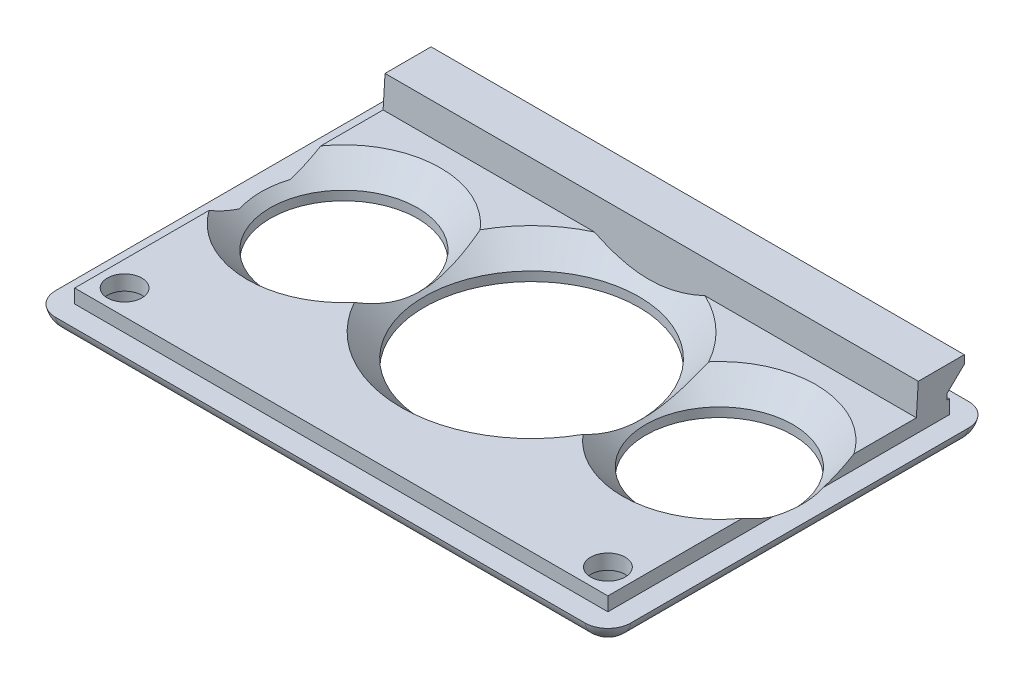
SolidWorks part; units mm, degrees
ref_plane "Front Plane" through (0, 0, 0) normal (0, 0, 1) x (1, 0, 0)
ref_plane "Top Plane" through (0, 0, 0) normal (0, 1, 0) x (1, 0, 0)
ref_plane "Right Plane" through (0, 0, 0) normal (1, 0, 0) x (0, 0, -1)
sketch "Sketch1" plane through (0, 0, 0) normal (0, 1, 0) x (1, 0, 0)
  line L1 (-1.2463, 1.173) -> (73.7537, 1.173)
  line L2 (-1.2463, 1.173) -> (-1.2463, 51.173)
  line L3 (-1.2463, 51.173) -> (73.7537, 51.173)
  line L4 (73.7537, 1.173) -> (73.7537, 51.173)
  dimension "D1" = 50
  dimension "D2" = 75
extrude "Boss-Extrude1" add sketch "Sketch1" along normal blind 2.4
sketch "Sketch2" plane through (0, 2.4, 0) normal (0, 1, 0) x (1, 0, 0)
  line L0 (36.2537, 51.173) -> (36.2537, 1.173) construction
  line L1 (73.7537, 51.173) -> (-1.2463, 51.173) construction
  line L2 (-1.2463, 1.173) -> (73.7537, 1.173) construction
  line L3 (-1.2463, 51.173) -> (-1.2463, 1.173) construction
  line L4 (1.5037, 48.423) -> (71.0037, 48.423)
  line L5 (1.5037, 48.423) -> (1.5037, 3.923)
  line L6 (1.5037, 3.923) -> (71.0037, 3.923)
  line L7 (71.0037, 48.423) -> (71.0037, 3.923)
  line L8 (1.5037, 48.423) -> (71.0037, 3.923) construction
  line L9 (1.5037, 3.923) -> (71.0037, 48.423) construction
  point P6 (36.2537, 26.173)
  dimension "D1" = 2.75
  dimension "D2" = 2.75
extrude "Boss-Extrude2" add sketch "Sketch2" along normal blind 1.8
sketch "Sketch3" [suppressed] plane through (0, 0, 0) normal (0, -1, 0) x (-1, 0, 0)
  line L1 (-74.0007, 57.8979) -> (-74.348, 7.8991) construction
  line L2 (-74.348, 7.8991) -> (0.6502, 7.3782) construction
  line L3 (0.6502, 7.3782) -> (0.9975, 57.377) construction
  line L4 (0.9975, 57.377) -> (-74.0007, 57.8979) construction
  circle A0 centre (-61.0257, 35.0904) radius 9.305
  circle A1 centre (-36.6576, 35.188) radius 13.2617
  circle A2 centre (-12.0957, 35.0904) radius 9.305
  circle A3 centre (-67.6316, 45.7049) radius 3.1
  circle A4 centre (-18.7016, 45.7049) radius 3.1
  circle A5 centre (-68.3065, 13.8573) radius 1.75
  circle A6 centre (-5.3158, 13.4277) radius 1.75
sketch "Sketch4" plane through (0, 0, 0) normal (0, -1, 0) x (-1, 0, 0)
  line L0 (-73.7537, 55.2723) -> (-73.7537, 1.173) construction
  line L1 (-73.7537, 1.173) -> (1.2463, 1.173) construction
  line L2 (-60.7187, 28.723) -> (-36.2537, 28.723) construction
  line L3 (-36.2537, 28.723) -> (-11.7887, 28.723) construction
  line L4 (-60.7187, 28.723) -> (-73.7537, 28.723) construction
  line L5 (-4.7537, 7.1809) -> (-67.7537, 7.173) construction
  line L6 (-67.7537, 7.173) -> (-73.7537, 7.173) construction
  line L7 (-73.7537, 7.173) -> (-67.7537, 7.173) construction
  line L8 (-67.7537, 7.173) -> (-67.7537, 1.173) construction
  line L9 (-67.7537, 1.173) -> (-67.7537, 7.173) construction
  line L10 (-67.7537, 7.173) -> (-67.7537, 28.723) construction
  line L11 (-11.7887, 28.723) -> (-28.1542, 28.723) construction
  line L12 (1.2463, 1.173) -> (-73.7537, 1.173) construction
  line L13 (-4.7537, 7.1809) -> (-4.7537, 1.173) construction
  line L14 (-4.7537, 1.173) -> (-4.7537, 7.1809) construction
  line L15 (-4.7537, 7.1809) -> (-4.7537, 28.723) construction
  line L16 (-73.7537, 1.173) -> (-73.7537, 51.173) construction
  circle A0 centre (-60.7187, 28.723) radius 9.6
  circle A1 centre (-36.2537, 28.723) radius 14
  circle A2 centre (-11.7887, 28.723) radius 9.6
  circle A3 centre (-67.7537, 7.173) radius 2.25
  circle A4 centre (-4.7537, 7.1809) radius 2.25
  dimension "D5" = 28
  dimension "D6" = 19.2
  dimension "D7" = 4.5
  dimension "D1" = 27.55
  dimension "D2" = 13.035
  dimension "D3" = 24.465
  dimension "D4" = 24.465
  dimension "D8" = 6
  dimension "D9" = 6
  dimension "D10" = 6
  dimension "D11" = 75
  dimension "D12" = 27.55
extrude "Cut-Extrude1" cut sketch "Sketch4" against normal through all
sketch "Sketch5" plane through (71.0037, 0, 0) normal (1, 0, 0) x (0, 0, -1)
  line L0 (48.123, 4.2) -> (44.123, 4.2)
  line L1 (3.923, 4.2) -> (48.423, 4.2) construction
  line L2 (44.123, 4.2) -> (44.373, 8.2)
  line L3 (44.373, 8.2) -> (50.373, 8.2)
  line L4 (50.373, 8.2) -> (50.373, 7.1)
  line L6 (48.1425, 4.9783) -> (48.123, 4.2)
  line L7 (48.423, 4.2) -> (48.423, 2.4) construction
  line L8 (51.173, 2.4) -> (51.173, 0) construction
  line L9 (48.1425, 4.9783) -> (50.373, 7.1)
  dimension "D1" = 1.1
  dimension "D2" = 4
  dimension "D3" = 0.3
  dimension "D4" = 0.8
  dimension "D5" = 4
  dimension "D6" = 6
  dimension "D8" = 135
extrude "Boss-Extrude3" add sketch "Sketch5" against normal up to surface (69.5 mm away) up to face at (1.5037, 3.3, -26.173)
sketch "Sketch6" plane through (0, 0, 0) normal (0, -1, 0) x (1, 0, 0)
  line L0 (67.3246, -42.4375) -> (67.3246, -36.2375) construction
  line L1 (73.7537, -1.173) -> (73.7537, -51.173) construction
  line L3 (73.7537, -51.173) -> (-1.2463, -51.173) construction
  line L4 (-1.2463, -51.173) -> (-1.2463, -1.173) construction
  circle A0 centre (67.3246, -39.3375) radius 3.65
  circle A1 centre (18.3946, -39.3375) radius 3.65
  dimension "D1" = 7.3
  dimension "D2" = 6.429
  dimension "D3" = 11.8356
  dimension "D4" = 19.641
  dimension "D5" = 11.8356
extrude "Cut-Extrude2" [suppressed] cut sketch "Sketch6" against normal through all
fillet "Fillet1" radius 3 4 edges at (-1.2463, 1.2, -51.173) (-1.2463, 1.2, -1.173) (73.7537, 1.2, -1.173) (73.7537, 1.2, -51.173)
fillet "Fillet2" radius 3 8 edges at (-0.3677, 0, -50.2943) (36.2537, 0, -51.173) (72.875, 0, -50.2943) (73.7537, 0, -26.173) (72.875, 0, -2.0517) (36.2537, 0, -1.173) (-0.3677, 0, -2.0517) (-1.2463, 0, -26.173)
sketch "Sketch7" plane through (0, 0, 0) normal (0, -1, 0) x (1, 0, 0)
  circle A0 centre (4.7537, -7.1809) radius 3
  circle A1 centre (67.7537, -7.173) radius 3
  dimension "D1" = 6
extrude "Cut-Extrude3" cut sketch "Sketch7" against normal blind 2.25
chamfer "Chamfer1" distance 3 angle 45 3 edges at (60.7187, 4.2, -38.323) (36.2537, 4.2, -42.723) (11.7887, 4.2, -38.323)
